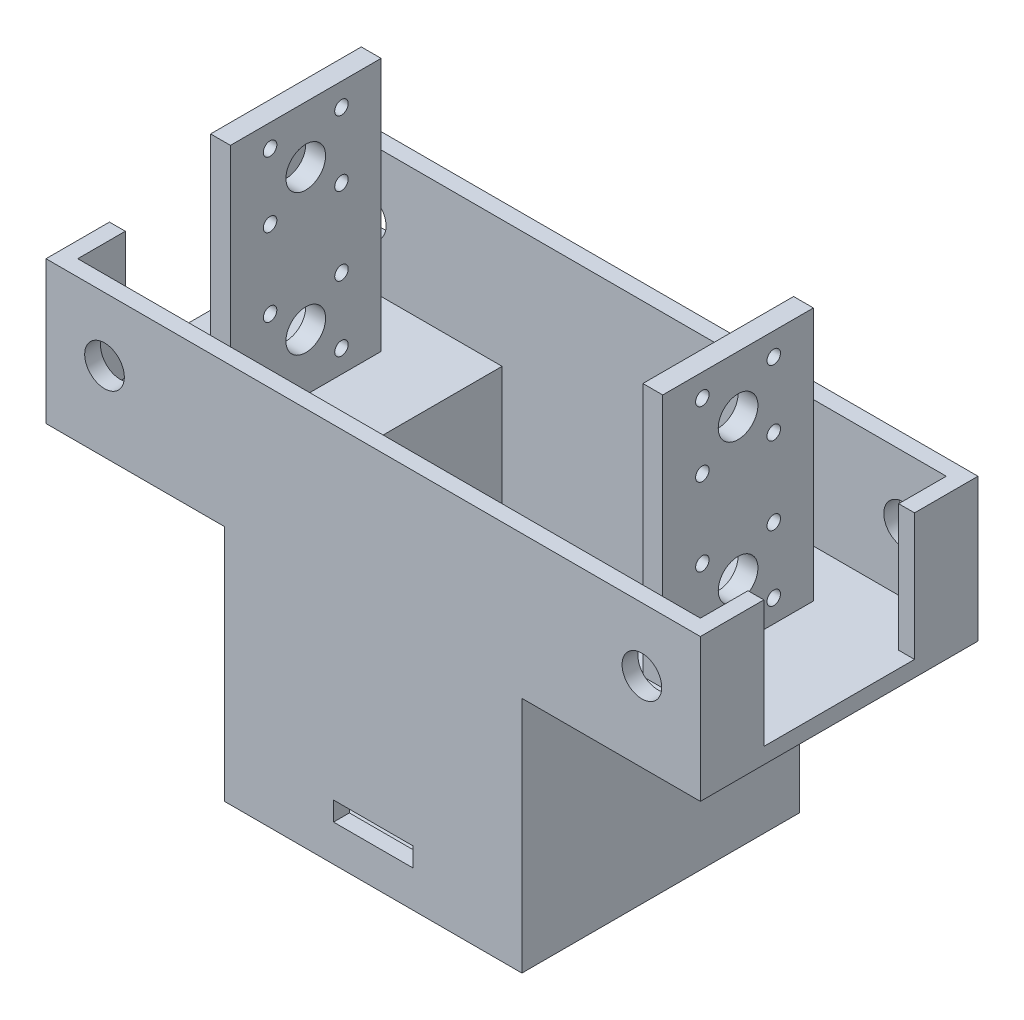
SolidWorks part; units mm, degrees
ref_plane "Front Plane" through (0, 0, 0) normal (0, 0, 1) x (1, 0, 0)
ref_plane "Top Plane" through (0, 0, 0) normal (0, 1, 0) x (1, 0, 0)
ref_plane "Right Plane" through (0, 0, 0) normal (1, 0, 0) x (0, 0, -1)
sketch "Sketch1" plane through (0, 0, 0) normal (0, 1, 0) x (1, 0, 0)
  line L0 (0, 0) -> (0, -14.43) construction
  line L1 (-37.5, 20) -> (37.5, 20)
  line L2 (-37.5, 20) -> (-37.5, -20)
  line L3 (-37.5, -20) -> (37.5, -20)
  line L4 (37.5, 20) -> (37.5, -20)
  line L5 (-37.5, 20) -> (37.5, -20) construction
  line L6 (-37.5, -20) -> (37.5, 20) construction
  line L7 (0, 0) -> (6.508, 0) construction
  line L8 (-2.5, 10) -> (2.5, 10)
  line L9 (-2.5, 10) -> (-2.5, -10)
  line L10 (-2.5, -10) -> (2.5, -10)
  line L11 (2.5, 10) -> (2.5, -10)
  line L12 (-2.5, 10) -> (2.5, -10) construction
  line L13 (-2.5, -10) -> (2.5, 10) construction
  circle A0 centre (-21, 0) radius 5
  circle A1 centre (-30, 8.25) radius 1.7
  circle A2 centre (-12, 8.25) radius 1.7
  circle A3 centre (-12, -8.25) radius 1.7
  circle A4 centre (-30, -8.25) radius 1.7
  circle A5 centre (12, 8.25) radius 1.7
  circle A6 centre (12, -8.25) radius 1.7
  circle A7 centre (21, 0) radius 5
  circle A8 centre (30, -8.25) radius 1.7
  circle A9 centre (30, 8.25) radius 1.7
  circle A10 centre (-30, -17.5) radius 1.1976
  circle A11 centre (-12, -17.5) radius 1.1976
  circle A12 centre (12, -17.5) radius 1.1976
  circle A13 centre (30, -17.5) radius 1.1976
  circle A14 centre (30, 17.5) radius 1.1976
  circle A15 centre (12, 17.5) radius 1.1976
  circle A16 centre (-12, 17.5) radius 1.1976
  circle A17 centre (-30, 17.5) radius 1.1976
  point P0 (0, 0)
  dimension "D3" = 10
  dimension "D4" = 21
  dimension "D5" = 8.25
  dimension "D6" = 9
  dimension "D9" = 5
  dimension "D11" = 20
  dimension "D12" = 7.5
  dimension "D13" = 25.5
  dimension "D14" = 7.5
  dimension "D15" = 2.5
  dimension "D1" = 75
  dimension "D2" = 40
  dimension "D10" = 20
  dimension "D7" = 2
  dimension "D8" = 2
  dimension "D16" = 2
extrude "Boss-Extrude1" add sketch "Sketch1" along normal blind 3
sketch "Sketch2" plane through (0, 3, 0) normal (0, 1, 0) x (1, 0, 0)
  line L0 (-37.5, 20) -> (-37.5, -20) construction
  line L1 (-33.5, 14) -> (33.5, 14)
  line L2 (-33.5, 14) -> (-33.5, -14)
  line L3 (-33.5, -14) -> (33.5, -14)
  line L4 (33.5, 14) -> (33.5, -14)
  line L5 (37.5, -20) -> (37.5, 20) construction
  line L6 (37.5, 20) -> (-37.5, 20) construction
  line L7 (-37.5, -20) -> (37.5, -20) construction
  dimension "D1" = 4
  dimension "D2" = 4
  dimension "D3" = 6
  dimension "D4" = 6
extrude "Cut-Extrude1" cut sketch "Sketch2" against normal through all both and the other way through all
sketch "Sketch3" plane through (0, 3, 0) normal (0, 1, 0) x (1, 0, 0)
  line L1 (37.5, 20) -> (-37.5, 20)
  line L2 (37.5, 20) -> (37.5, 35)
  line L3 (37.5, 35) -> (-37.5, 35)
  line L4 (-37.5, 20) -> (-37.5, 35)
  line L5 (-37.5, -20) -> (37.5, -20)
  line L6 (-37.5, -20) -> (-37.5, -35)
  line L7 (-37.5, -35) -> (37.5, -35)
  line L8 (37.5, -20) -> (37.5, -35)
  line L10 (-37.5, 20) -> (-33.5, 20)
  line L11 (-37.5, 20) -> (-37.5, -20)
  line L12 (-37.5, -20) -> (-33.5, -20)
  line L13 (-33.5, 20) -> (-33.5, -20)
  line L14 (37.5, 20) -> (33.5, 20)
  line L15 (37.5, 20) -> (37.5, -20)
  line L16 (37.5, -20) -> (33.5, -20)
  line L17 (33.5, 20) -> (33.5, -20)
  line M3 (-33.5, -14) -> (-33.5, 14)
  line M5 (33.5, 14) -> (33.5, -14)
  line M11 (37.5, -20) -> (37.5, 20)
  line M12 (37.5, 20) -> (-37.5, 20)
  line M13 (-37.5, 20) -> (-37.5, -20)
  line M14 (-37.5, -20) -> (37.5, -20)
  dimension "D1" = 15
  dimension "D2" = 15
extrude "Boss-Extrude3" add sketch "Sketch3" along normal blind 90 and the other way blind 3 contours L8 L5 L6 L7 M14 | L4 L1 L2 L3 M12 | L17 M12 M5 M14 M11 | L13 L1 M13 M14 M3 region at (35.5, 3, 0) region at (0, 3, -27.5) region at (0, 3, 27.5) region at (-35.5, 3, 0)
sketch "Sketch6" plane through (0, 3, 0) normal (0, 1, 0) x (1, 0, 0)
  line L0 (-37.5, -35) -> (37.5, -35) construction
  line L1 (-33.5, -20) -> (33.5, -20)
  line L2 (-33.5, -20) -> (-33.5, -31)
  line L3 (-33.5, -31) -> (33.5, -31)
  line L4 (33.5, -20) -> (33.5, -31)
  line L5 (33.5, 20) -> (-33.5, 20)
  line L6 (33.5, 20) -> (33.5, 31)
  line L7 (33.5, 31) -> (-33.5, 31)
  line L8 (-33.5, 20) -> (-33.5, 31)
  line L9 (37.5, 35) -> (-37.5, 35) construction
  dimension "D1" = 4
  dimension "D2" = 4
extrude "Cut-Extrude4" cut sketch "Sketch6" along normal through all
sketch "Sketch7" plane through (-37.5, 0, 0) normal (-1, 0, 0) x (0, 0, 1)
  line L0 (35, 0) -> (35, 93) construction
  line L1 (-35, 93) -> (35, 93)
  line L2 (-35, 93) -> (-35, 56)
  line L3 (-35, 56) -> (35, 56)
  line L4 (35, 93) -> (35, 56)
  dimension "D1" = 37
extrude "Boss-Extrude4" add sketch "Sketch7" along normal blind 45
ref_plane "Plane1" through (0, 0, 0) normal (1, 0, 0) x (0, 0, -1)
mirror "Mirror2" about plane through (0, 0, 0) normal (1, 0, 0) of "Boss-Extrude4"
sketch "Sketch8" plane through (0, 93, 0) normal (0, 1, 0) x (1, 0, 0)
  line L0 (-82.5, -35) -> (-82.5, 35) construction
  line L1 (-33.5, 31) -> (-78.5, 31)
  line L2 (-33.5, 31) -> (-33.5, -31)
  line L3 (-33.5, -31) -> (-78.5, -31)
  line L4 (-78.5, 31) -> (-78.5, -31)
  line L5 (33.5, -31) -> (78.5, -31)
  line L6 (33.5, -31) -> (33.5, 31)
  line L7 (33.5, 31) -> (78.5, 31)
  line L8 (78.5, -31) -> (78.5, 31)
  line L9 (82.5, -35) -> (82.5, 35) construction
  dimension "D1" = 4
  dimension "D2" = 4
extrude "Cut-Extrude6" cut sketch "Sketch8" against normal blind 29
sketch "Sketch9" plane through (-82.5, 0, 0) normal (-1, 0, 0) x (0, 0, 1)
  line L18 (-31, 64) -> (31, 64) construction
  line L19 (-19, 64) -> (19, 64)
  line L20 (-19, 64) -> (-19, 92.5)
  line L21 (-19, 92.5) -> (19, 92.5)
  line L22 (19, 64) -> (19, 92.5)
  line L25 (-31, 64) -> (-31, 93) construction
  dimension "D1" = 38
  dimension "D2" = 12
  dimension "D3" = 28.5
sketch "Sketch11" plane through (0, 0, 35) normal (0, 0, 1) x (1, 0, 0)
  line L0 (82.5, 56) -> (82.5, 93) construction
  line L1 (-82.5, 56) -> (-37.5, 56)
  line L2 (-82.5, 56) -> (-82.5, 60)
  line L3 (-82.5, 60) -> (-37.5, 60)
  line L4 (-37.5, 56) -> (-37.5, 60)
  line L5 (37.5, 56) -> (82.5, 56)
  line L6 (37.5, 56) -> (37.5, 60)
  line L7 (37.5, 60) -> (82.5, 60)
  line L8 (82.5, 56) -> (82.5, 60)
  line L11 (-78.5, 64) -> (-33.5, 64) construction
  line L12 (33.5, 64) -> (78.5, 64) construction
  dimension "D1" = 4
  dimension "D2" = 4
extrude "Cut-Extrude9" cut sketch "Sketch11" against normal through all
extrude "Cut-Extrude10" cut sketch "Sketch9" against normal through all
sketch "Sketch13" plane through (0, 64, 0) normal (0, 1, 0) x (1, 0, 0)
  line L0 (-78.5, 31) -> (-78.5, -31) construction
  line L1 (-57, 19) -> (-52, 19)
  line L2 (-57, 19) -> (-57, -19)
  line L3 (-57, -19) -> (-52, -19)
  line L4 (-52, 19) -> (-52, -19)
  line L7 (78.5, 31) -> (-78.5, 31) construction
  line L13 (-57, -19) -> (-57, 19)
  line L17 (-82.5, -19) -> (-107.5, -19)
  line L18 (-82.5, -19) -> (-82.5, 19)
  line L19 (-82.5, 19) -> (-107.5, 19)
  line L20 (-107.5, -19) -> (-107.5, 19)
  line L21 (-107.5, 19) -> (-61, 19)
  line L22 (-107.5, 19) -> (-107.5, -19)
  line L23 (-107.5, -19) -> (-61, -19)
  line L24 (-61, 19) -> (-61, -19)
  dimension "D1" = 21.5
  dimension "D2" = 5
  dimension "D3" = 38
  dimension "D4" = 12
  dimension "D5" = 25
  dimension "D6" = 46.5
extrude "Boss-Extrude5" add sketch "Sketch13" along normal blind 32 contours L4 L1 L2 L3 region at (-54.5, 64, 0)
sketch "Sketch14" plane through (-57, 0, 0) normal (-1, 0, 0) x (0, 0, 1)
  line L0 (-19, 96) -> (-19, 64) construction
  line L1 (-19, 64) -> (19, 64) construction
  circle A0 centre (0, 78.25) radius 5
  circle A1 centre (-9, 86.2021) radius 1.7
  circle A2 centre (9, 86.2021) radius 1.7
  circle A3 centre (9, 69.7021) radius 1.7
  circle A4 centre (-9, 69.7021) radius 1.7
  dimension "D1" = 19
  dimension "D2" = 9
  dimension "D3" = 14.25
extrude "Cut-Extrude11" cut sketch "Sketch14" against normal blind 32
mirror "Mirror4" about plane through (0, 0, 0) normal (1, 0, 0) of "Boss-Extrude5", "Cut-Extrude11"
sketch "Sketch15" plane through (0, 93, 0) normal (0, 1, 0) x (1, 0, 0)
  line L1 (-82.5, 35) -> (82.5, 35)
  line L2 (-82.5, 35) -> (-82.5, -35)
  line L3 (-82.5, -35) -> (82.5, -35)
  line L4 (82.5, 35) -> (82.5, -35)
  line L5 (-78.5, 31) -> (78.5, 31)
  line L6 (-78.5, 31) -> (-78.5, -31)
  line L7 (-78.5, -31) -> (78.5, -31)
  line L8 (78.5, 31) -> (78.5, -31)
extrude "Boss-Extrude6" add sketch "Sketch15" along normal blind 3
sketch "Sketch16" plane through (0, 0, 35) normal (0, 0, 1) x (1, 0, 0)
  line L1 (-10, 14.0464) -> (10, 14.0464)
  line L2 (-10, 14.0464) -> (-10, 9.2258)
  line L3 (-10, 9.2258) -> (10, 9.2258)
  line L4 (10, 14.0464) -> (10, 9.2258)
  line L5 (-37.5, 0) -> (-37.5, 60) construction
  dimension "D1" = 20
  dimension "D2" = 27.5
extrude "Cut-Extrude12" cut sketch "Sketch16" against normal through all
sketch "Sketch18" plane through (0, 0, 35) normal (0, 0, 1) x (1, 0, 0)
  line L0 (57, 96) -> (57, 64) construction
  line L2 (33.5, 64) -> (78.5, 64) construction
  circle A0 centre (67.75, 80) radius 5
  dimension "D1" = 10.75
  dimension "D2" = 16
  dimension "D3" = 10
extrude "Cut-Extrude14" cut sketch "Sketch18" against normal through all
mirror "Mirror5" about plane through (0, 0, 0) normal (1, 0, 0) of "Cut-Extrude14"
mirror "Mirror6" about plane through (0, 96, 0) normal (0, 1, 0) of "Mirror4"
sketch "Sketch19" plane through (82.5, 0, 0) normal (1, 0, 0) x (0, 0, -1)
  line L0 (19, 128) -> (19, 64) construction
  line L1 (-19, 92.5) -> (19, 92.5)
  line L2 (-19, 92.5) -> (-19, 96)
  line L3 (-19, 96) -> (19, 96)
  line L4 (19, 92.5) -> (19, 96)
extrude "Cut-Extrude15" cut sketch "Sketch19" against normal blind 10
mirror "Mirror7" about plane through (0, 0, 0) normal (1, 0, 0) of "Cut-Extrude15"
